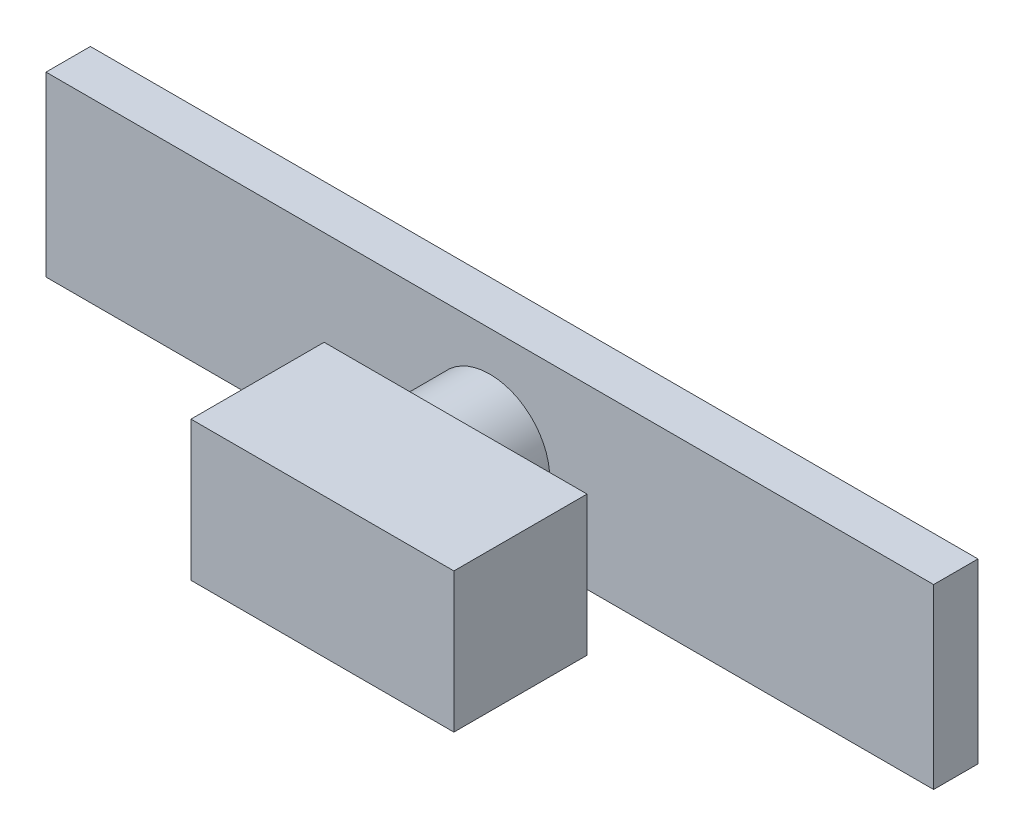
SolidWorks part; units mm, degrees
ref_plane "Front Plane" through (0, 0, 0) normal (0, 0, 1) x (1, 0, 0)
ref_plane "Top Plane" through (0, 0, 0) normal (0, 1, 0) x (1, 0, 0)
ref_plane "Right Plane" through (0, 0, 0) normal (1, 0, 0) x (0, 0, -1)
sketch "Sketch2" plane through (0, 0, 0) normal (0, 0, 1) x (1, 0, 0)
  line L1 (-47.8692, 21.2481) -> (206.1308, 21.2481)
  line L2 (-47.8692, 21.2481) -> (-47.8692, 8.5481)
  line L3 (-47.8692, 8.5481) -> (206.1308, 8.5481)
  line L4 (206.1308, 21.2481) -> (206.1308, 8.5481)
  dimension "D1" = 12.7
  dimension "D2" = 254
extrude "Boss-Extrude1" add sketch "Sketch2" along normal blind 50.8
sketch "Sketch3" plane through (0, 21.2481, 0) normal (0, 1, 0) x (1, 0, 0)
  circle A0 centre (79.1308, -28.4831) radius 17.1408
extrude "Boss-Extrude2" add sketch "Sketch3" along normal blind 19.05
sketch "Sketch4" plane through (0, 40.2981, 0) normal (0, 1, 0) x (1, 0, 0)
  line L1 (50.7675, -8.111) -> (126.0034, -8.111)
  line L2 (50.7675, -8.111) -> (50.7675, -48.0661)
  line L3 (50.7675, -48.0661) -> (126.0034, -48.0661)
  line L4 (126.0034, -8.111) -> (126.0034, -48.0661)
extrude "Boss-Extrude3" add sketch "Sketch4" along normal blind 38.1
scale "Scale2" scale about centroid uniform scaling yes scale factor 0.06
move or copy body "Body-Move/Copy1" bodies to move or copy 105 copy no rotation origin (0, 33.6669, 26.5501) rotation axis (1, 0, 0) rotation angle 90
move or copy body "Body-Move/Copy3" bodies to move or copy 106 copy no translate (-50.8, 0, -50.8)
scale "Scale5" scale about centroid uniform scaling yes scale factor 0.25
move or copy body "Body-Move/Copy9" bodies to move or copy 111 copy no translate (-50.8, 0, 0)
move or copy body "Body-Move/Copy11" bodies to move or copy 117 copy no translate (0, 0, -50.8)
